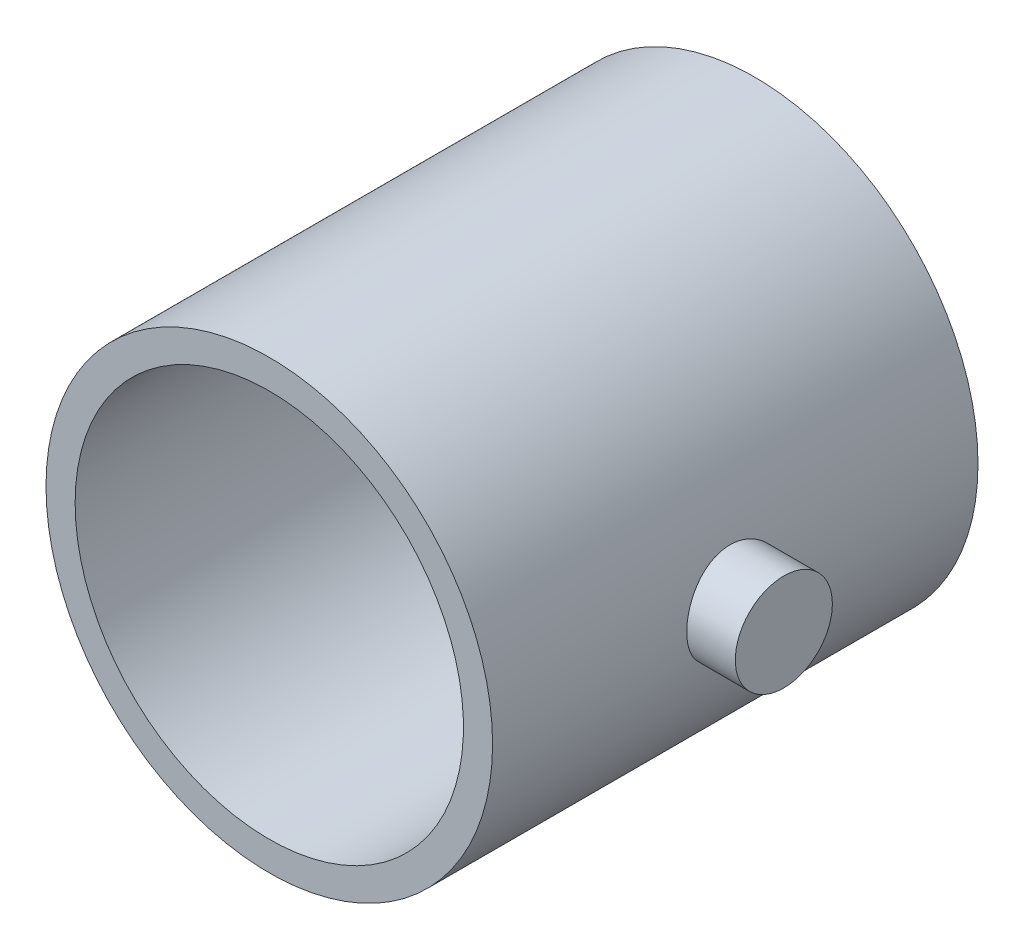
SolidWorks part; units mm, degrees
ref_plane "Front" through (0, 0, 0) normal (0, 0, 1) x (1, 0, 0)
ref_plane "Top" through (0, 0, 0) normal (0, 1, 0) x (1, 0, 0)
ref_plane "Right" through (0, 0, 0) normal (1, 0, 0) x (0, 0, -1)
sketch "Esquisse1" plane through (0, 0, 0) normal (0, 0, 1) x (1, 0, 0)
  circle A0 centre (0, 0) radius 20
  circle A1 centre (0, 0) radius 23
  dimension "D1" = 40
  dimension "D2" = 3
extrude "Boss.-Extru.1" add sketch "Esquisse1" along normal mid plane 50
ref_plane "Plan1" through (23, 0, 0) normal (1, 0, 0) x (0, 0, -1)
sketch "Esquisse2" plane through (23, 0, 0) normal (1, 0, 0) x (0, 0, -1)
  circle A0 centre (0, 0) radius 5
  dimension "D1" = 10
extrude "Boss.-Extru.2" add sketch "Esquisse2" against normal up to surface and the other way blind 5 up to face at (23, 0, 25)
sketch "Esquisse3" plane through (0, 0, 0) normal (0, 1, 0) x (1, 0, 0)
  line L0 (28, 0) -> (53, 0)
  line L1 (28, -5) -> (28, 5) construction
  line L2 (96.3013, 25) -> (133.8013, 89.9519)
  arc A0 (53, 0) -> (96.3013, 25) centre (53, 50) ccw
  arc A1 (133.8013, 89.9519) -> (155.4805, 110.035) centre (177.1025, 64.9519) cw
  dimension "D1" = 25
  dimension "D2" = 50
  dimension "D4" = 50
  dimension "D3" = 75
  dimension "D5" = 120
  dimension "D6" = 30
sketch "Esquisse4" plane through (28, 0, 0) normal (1, 0, 0) x (0, 0, -1)
  circle A0 centre (0, 0) radius 2.5
  dimension "D1" = 5
sweep "Balayage1" [suppressed] add profiles "Esquisse4" path "Esquisse3"
